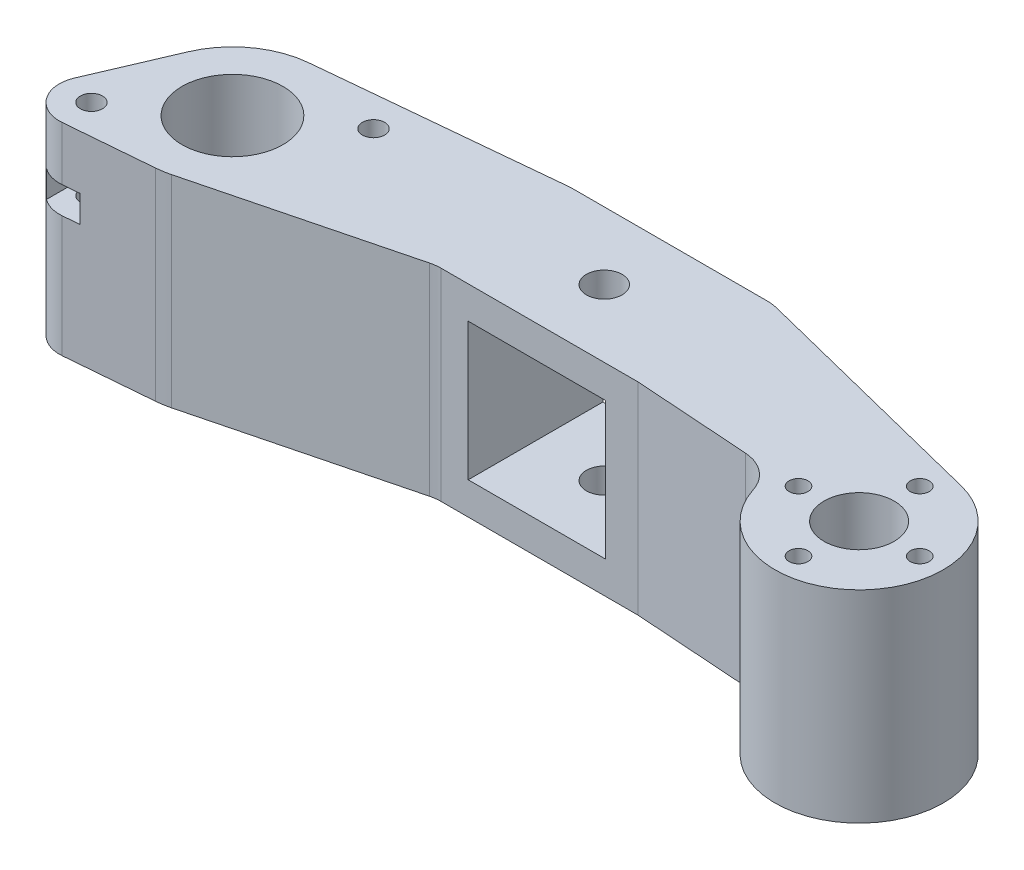
SolidWorks part; units mm, degrees
ref_plane "Front Plane" through (0, 0, 0) normal (0, 0, 1) x (1, 0, 0)
ref_plane "Top Plane" through (0, 0, 0) normal (0, 1, 0) x (1, 0, 0)
ref_plane "Right Plane" through (0, 0, 0) normal (1, 0, 0) x (0, 0, -1)
sketch "Sketch1" plane through (0, 0, 0) normal (0, 0, 1) x (1, 0, 0)
  line L1 (-10.2, 10.2) -> (10.2, 10.2)
  line L2 (-10.2, 10.2) -> (-10.2, -10.2)
  line L3 (-10.2, -10.2) -> (10.2, -10.2)
  line L4 (10.2, 10.2) -> (10.2, -10.2)
  line L5 (-10.2, 10.2) -> (10.2, -10.2) construction
  line L6 (-10.2, -10.2) -> (10.2, 10.2) construction
  line L7 (15, -15) -> (-15, -15)
  line L8 (15, -15) -> (15, 15)
  line L9 (15, 15) -> (-15, 15)
  line L10 (-15, -15) -> (-15, 15)
  line L11 (15, -15) -> (-15, 15) construction
  line L12 (15, 15) -> (-15, -15) construction
  point P0 (0, 0)
  point P6 (0, 0)
  dimension "D1" = 20.4
  dimension "D2" = 20.4
  dimension "D3" = 30
extrude "Boss-Extrude1" add sketch "Sketch1" along normal blind 20
sketch "Sketch2" plane through (0, 15, 0) normal (0, 1, 0) x (1, 0, 0)
  line L0 (0, 0) -> (0, -10) construction
  circle A0 centre (0, -10) radius 2.65
  dimension "D2" = 5.3
  dimension "D1" = 10
extrude "Cut-Extrude1" cut sketch "Sketch2" against normal through all
sketch "Sketch3" plane through (0, 15, 0) normal (0, 1, 0) x (1, 0, 0)
  line L0 (-65.8966, -22.761) -> (-60.8377, -10.9415)
  line L2 (-61.1079, -29.3953) -> (-48.2966, -28.3159)
  line L3 (-46.2568, -27.9722) -> (-15, -20)
  line L4 (-15, -20) -> (15, -20)
  line L5 (-37.1835, -7.0809) -> (-61.5086, -24.6391) construction
  line L6 (15, -20) -> (36.8461, -21.5)
  line L7 (-50.5424, -3.4174) -> (-15, 0)
  line L8 (0, -11.7298) -> (0, -10) construction
  line L9 (15, 0) -> (52.3865, -9.3754)
  line L10 (-15, 0) -> (-12.7035, -14.6487)
  line L11 (-12.7035, -14.6487) -> (12.9548, -14.6487)
  line L12 (12.9548, -14.6487) -> (15, 0)
  line L13 (-49.3461, -10) -> (49.3461, -10) construction
  line L14 (49.3461, -10) -> (49.3461, -21.5) construction
  line L15 (-49.3461, -10) -> (-49.3461, -15.86) construction
  circle A0 centre (-49.3461, -15.86) radius 7.5
  circle A1 centre (-61.5086, -24.6391) radius 4.773
  circle A2 centre (-49.3461, -15.86) radius 12.5
  circle A3 centre (-61.5086, -24.6391) radius 1.65
  circle A4 centre (-37.1835, -7.0809) radius 1.65
  circle A5 centre (49.3461, -21.5) radius 5.2
  circle A6 centre (49.3461, -21.5) radius 9 construction
  circle A7 centre (49.3461, -30.5) radius 1.4
  circle A8 centre (40.3461, -21.5) radius 1.4
  circle A9 centre (49.3461, -12.5) radius 1.4
  circle A10 centre (58.3461, -21.5) radius 1.4
  circle A11 centre (49.3461, -21.5) radius 12.5
  circle A16 centre (0, -10) radius 2.65 construction
  point P15 (-49.3461, -15.86)
  point P18 (0, 0)
  point P31 (49.3461, -21.5)
  point P37 (0, 0)
  point P38 (0, -10)
  dimension "D1" = 15
  dimension "D2" = 25
  dimension "D5" = 3.3
  dimension "D6" = 10.4
  dimension "D7" = 18
  dimension "D8" = 2.8
  dimension "D3" = 30
  dimension "D4" = 5.86
  dimension "D9" = 4
extrude "Boss-Extrude2" add sketch "Sketch3" against normal blind 30
sketch "Sketch4" plane through (0, 0, 0) normal (0, 0, -1) x (-1, 0, 0)
  line L1 (10.2, -10.2) -> (-10.2, -10.2)
  line L2 (10.2, -10.2) -> (10.2, 10.2)
  line L3 (10.2, 10.2) -> (-10.2, 10.2)
  line L4 (-10.2, -10.2) -> (-10.2, 10.2)
  line L5 (10.2, -10.2) -> (-10.2, 10.2) construction
  line L6 (10.2, 10.2) -> (-10.2, -10.2) construction
  point P0 (0, 0)
sketch "Sketch5" plane through (0, 15, 0) normal (0, 1, 0) x (1, 0, 0)
  line L1 (-37.1835, -10.3809) -> (-34.3256, -8.7309)
  line L2 (-34.3256, -8.7309) -> (-34.3256, -5.4309)
  line L3 (-34.3256, -5.4309) -> (-37.1835, -3.7809)
  line L4 (-37.1835, -3.7809) -> (-40.0414, -5.4309)
  line L5 (-40.0414, -5.4309) -> (-40.0414, -8.7309)
  line L6 (-40.0414, -8.7309) -> (-37.1835, -10.3809)
  line L7 (-61.5086, -27.9391) -> (-58.6507, -26.2891)
  line L8 (-58.6507, -26.2891) -> (-58.6507, -22.9891)
  line L9 (-58.6507, -22.9891) -> (-61.5086, -21.3391)
  line L10 (-61.5086, -21.3391) -> (-64.3665, -22.9891)
  line L11 (-64.3665, -22.9891) -> (-64.3665, -26.2891)
  line L12 (-64.3665, -26.2891) -> (-61.5086, -27.9391)
  line L13 (-64.3665, -22.9891) -> (-58.6507, -22.9891)
  line L14 (-64.3665, -22.9891) -> (-64.3665, -31.8207)
  line L15 (-64.3665, -31.8207) -> (-58.6507, -31.8207)
  line L16 (-58.6507, -22.9891) -> (-58.6507, -31.8207)
  line L17 (-40.0414, -8.7309) -> (-34.3256, -8.7309)
  line L18 (-40.0414, -8.7309) -> (-40.0414, 4.1534)
  line L19 (-40.0414, 4.1534) -> (-34.3256, 4.1534)
  line L20 (-34.3256, -8.7309) -> (-34.3256, 4.1534)
  circle A0 centre (-37.1835, -7.0809) radius 2.8579 construction
  circle A1 centre (-61.5086, -24.6391) radius 2.8579 construction
  circle M3 centre (-37.1835, -7.0809) radius 1.65
  line M5 (-15, 0) -> (-50.5424, -3.4174)
  circle M15 centre (-61.5086, -24.6391) radius 1.65
  line M51 (-61.1079, -29.3953) -> (-48.2966, -28.3159)
  arc M52 (-65.8966, -22.761) -> (-61.1079, -29.3953) centre (-61.5086, -24.6391) ccw
  dimension "D1" = 3.3
extrude "Cut-Extrude5" cut sketch "Sketch5" against normal blind 4 from offset 8 contours L13 L11 L12 L7 L8 M15 | L16 L14 L15 M51 M52 | L10 L13 L9 | M15 | L16 L7 L12 L14 M52 M51 | L3 L20 L18 L4 M5 | L5 L17 L2 L3 L4 M3 | L17 L6 L1 | M3 | L20 L19 L18 M5 offset against normal yes
fillet "Fillet1" radius 6 4 edges at (15, 0, 0) (-15, 0, 0) (-15, 0, 20) (36.8461, 0, 21.5)
